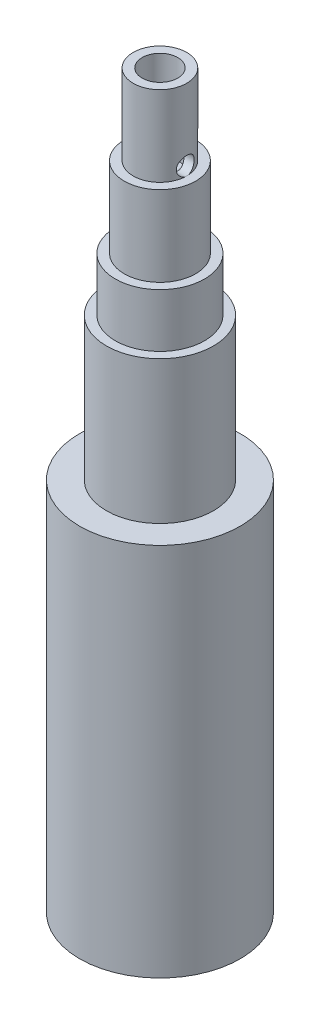
SolidWorks part; units mm, degrees
material "Plain Carbon Steel"
ref_plane "Front Plane" through (0, 0, 0) normal (0, 0, 1) x (1, 0, 0)
ref_plane "Top Plane" through (0, 0, 0) normal (0, 1, 0) x (1, 0, 0)
ref_plane "Right Plane" through (0, 0, 0) normal (1, 0, 0) x (0, 0, -1)
sketch "Sketch1" plane through (0, 0, 0) normal (0, 1, 0) x (1, 0, 0)
  circle A0 centre (0, 0) radius 9
  dimension "D1" = 18
extrude "base section" add sketch "Sketch1" along normal blind 42
sketch "Sketch2" plane through (0, 42, 0) normal (0, 1, 0) x (1, 0, 0)
  circle A0 centre (0, 0) radius 6
  dimension "D1" = 12
extrude "second section" add sketch "Sketch2" along normal blind 16
sketch "Sketch3" plane through (0, 58, 0) normal (0, 1, 0) x (1, 0, 0)
  circle A0 centre (0, 0) radius 5
  dimension "D1" = 10
extrude "bearing section" add sketch "Sketch3" along normal blind 6
sketch "Sketch4" plane through (0, 64, 0) normal (0, 1, 0) x (1, 0, 0)
  circle A0 centre (0, 0) radius 4
  dimension "D1" = 8
extrude "seal section" add sketch "Sketch4" along normal blind 9
sketch "Sketch5" plane through (0, 73, 0) normal (0, 1, 0) x (1, 0, 0)
  circle A0 centre (0, 0) radius 3
  dimension "D1" = 6
extrude "impeller section" add sketch "Sketch5" along normal blind 9
sketch "Sketch6" plane through (0, 82, 0) normal (0, 1, 0) x (1, 0, 0)
  circle A0 centre (0, 0) radius 2
  dimension "D1" = 4
extrude "impeller screw hole" cut sketch "Sketch6" against normal blind 10
sketch "Sketch7" plane through (0, 0, 0) normal (0, -1, 0) x (-1, 0, 0)
  circle A0 centre (0, 0) radius 4
  dimension "D1" = 8
extrude "motor shaft hole" cut sketch "Sketch7" against normal blind 32
sketch "Sketch8" plane through (0, 0, 0) normal (1, 0, 0) x (0, 0, -1)
  line L0 (0, 82) -> (0, 73) construction
  line L1 (3, 82) -> (-3, 82) construction
  line L2 (4, 73) -> (-4, 73) construction
  circle A0 centre (0, 74) radius 1
  dimension "D1" = 2
extrude "impeller dowel hole" cut sketch "Sketch8" against normal blind 10 and the other way blind 10
sketch "Sketch9" plane through (0, 0, 0) normal (1, 0, 0) x (0, 0, -1)
  line L0 (0, 32) -> (0, 0) construction
  line L1 (-4, 32) -> (4, 32) construction
  circle A0 centre (0, 29) radius 3
  circle A1 centre (0, 18.3333) radius 3
  dimension "D1" = 6
  dimension "D2" = 10.6667
extrude "set screw holes" cut sketch "Sketch9" against normal blind 20
equation "\"D1@Sketch1\"=\"coupler shaft base diameter\""
equation "\"bearing OD\" = 20mm"
equation "\"bearing outer race thickness\"= 1mm"
equation "\"bearing ID\"= 10mm"
equation "\"bearing depth\"= 6mm"
equation "\"bearing inner race thickness\"= 1mm"
equation "\"seal OD\" = 20mm"
equation "\"seal ID\"= 8mm"
equation "\"seal depth\"= 6mm"
equation "\"impeller base outer diameter\"= 1.75in"
equation "\"impeller base outer thickness\"= 1mm"
equation "\"impeller base center thickness\"= 5mm"
equation "\"impeller number of vanes\"= 8"
equation "\"impeller vane inner height\"= 8mm"
equation "\"impeller primary vane opening diamater\"= 10mm"
equation "\"impeller vane inner thickness\"= .75mm"
equation "\"impeller vane outer thickness\"= 1.5mm"
equation "\"impeller primary vane entrance angle\"= 20deg"
equation "\"impeller secondary vane entrance angle\"= 20deg"
equation "\"impeller secondary vane opening diameter\"= 10mm"
equation "\"motor to housing distance\"= 60mm"
equation "\"motor mount pattern diameter\"= 30mm"
equation "\"motor mount coupler shaft hole diameter\"= \"coupler shaft base diameter\"+ 4mm"
equation "\"motor mount to housing m8 screw hole diameter\"= 8.5mm"
equation "\"motor mount to housing m8 screw post radius\"= ( 3 * \"motor mount to housing m8 screw hole diameter\" ) / 2"
equation "\"motor mount to housing m8 pattern diameter\"= 100mm"
equation "\"motor mount to housing m4 screw hole diamater\"= 4mm"
equation "\"motor mount to housing m4 head diameter\"= 7.25mm"
equation "\"motor mount to housing m4 head depth\"= 4mm"
equation "\"motor mount plate thickness\"= 6mm + \"motor mount to housing m4 head depth\""
equation "\"motor shaft pride\"= 32mm"
equation "\"motor shaft flat section length from tip\"= 25.7mm"
equation "\"motor shaft bore end clearance\"= 2mm"
equation "\"motor mount shaft hole depth\"= \"motor shaft pride\""
equation "\"coupler shaft set screw drill hole diameter\"= 6mm"
equation "\"coupler shaft motor shaft hole diameter\"= 8mm"
equation "\"coupler shaft base diameter\"= 18mm"
equation "\"coupler shaft base length\"= \"motor mount shaft hole depth\" + 10mm"
equation "\"coupler shaft second section diameter\"= \"bearing ID\" + \"bearing inner race thickness\" * 2"
equation "\"coupler shaft third section diamater\"= \"bearing ID\""
equation "\"coupler shaft second section length\"= \"motor to housing distance\" -  \"coupler shaft base length\" - 2mm"
equation "\"coupler shaft set screw 1 distance\"= \"motor mount shaft hole depth\" / 3"
equation "\"coupler shaft set screw 2 distance\"= \"motor mount shaft hole depth\" * 4 / 5"
equation "\"housing bearing seat lip thickness\" = 2mm"
equation "\"housing base thickness\"= \"housing bearing seat lip thickness\" + \"seal depth\" + \"bearing depth\""
equation "\"housing top impeller vertical clearance\"= .5mm"
equation "\"housing top impeller horizontal clearance\"= .5mm"
equation "\"housing top impeller bottom clearance\"= 1mm"
equation "\"housing top impeller cavity height\"= \"housing top impeller bottom clearance\" + \"impeller base center thickness\" + \"impeller vane inner height\" + \"housing top impeller vertical clearance\""
equation "\"housing top impeller cavity diameter\"= 2 * \"housing top impeller horizontal clearance\" + \"impeller base outer diameter\""
equation "\"housing top impeller cavity tip height\"= \"housing top impeller bottom clearance\" + \"housing top impeller vertical clearance\" + \"impeller base outer thickness\" + \"impeller vane outer height\""
equation "\"housing top entrance OD\"= 20mm"
equation "\"housing top exit OD\"= 5mm"
equation "\"housing top o-ring channel height\"= 1.5mm"
equation "\"housing top o ring channel width\"= 1.5mm"
equation "\"housing top threaded inlet depth\"= 8mm"
equation "\"housing top total thickness\"= \"housing top threaded inlet depth\" + \"housing top impeller cavity height\""
equation "\"housing top total width\"= 10mm"
equation "\"housing top exit threaded diameter\"= 8mm"
equation "\"housing top exit threaded depth\"= 8mm"
equation "\"coupler shaft third section length\"= \"bearing depth\""
equation "\"coupler shaft seal section diameter\" = \"seal ID\""
equation "\"coupler shaft seal section length\" = \"housing base thickness\"+\"housing top impeller bottom clearance\"-\"bearing depth\""
equation "\"coupler shaft impeller section diameter\" = 6mm"
equation "\"coupler shaft impeller section length\" = \"impeller boss depth\"+\"impeller base center thickness\" - 1mm"
equation "\"D1@base section\" = \"coupler shaft base length\""
equation "\"D1@Sketch2\"=\"coupler shaft second section diameter\""
equation "\"D1@second section\" = \"coupler shaft second section length\""
equation "\"D1@Sketch3\"=\"coupler shaft third section diamater\""
equation "\"D1@bearing section\" = \"coupler shaft third section length\""
equation "\"D1@Sketch4\"=\"coupler shaft seal section diameter\""
equation "\"D1@seal section\" = \"coupler shaft seal section length\""
equation "\"D1@Sketch5\"=\"coupler shaft impeller section diameter\""
equation "\"D1@impeller section\" = \"coupler shaft impeller section length\""
equation "\"coupler shaft impeller screw hole diameter\" = \"motor mount to housing m4 screw hole diamater\""
equation "\"coupler shaft impeller screw hole depth\" = 10mm"
equation "\"D1@Sketch6\"=\"coupler shaft impeller screw hole diameter\""
equation "\"D1@impeller screw hole\" = \"coupler shaft impeller screw hole depth\""
equation "\"D1@Sketch7\"=\"coupler shaft motor shaft hole diameter\""
equation "\"D1@motor shaft hole\" = \"motor mount shaft hole depth\""
equation "\"impeller vane outer height\"= 4mm"
equation "\"impeller bolt surface height\" = 5mm"
equation "\"impeller bolt surface diameter\" = 8mm"
equation "\"housing top o-ring circumference\" = 250mm"
equation "\"housing top o-ring radius\" = (\"housing top o-ring circumference\")/(2*3.14)"
equation "\"coupler shaft to motor clearance\" = 2mm"
equation "\"impeller dowel diameter\" = 2mm"
equation "\"impeller dowel length\" = 2mm*2 + \"coupler shaft impeller section diameter\""
equation "\"D1@Sketch8\"=\"impeller dowel diameter\""
equation "\"D1@Sketch9\"=\"coupler shaft set screw drill hole diameter\""
equation "\"D2@Sketch9\"=\"coupler shaft set screw 1 distance\""
equation "\"impeller boss depth\" = 5mm"
equation "\"impeller boss diameter\" = \"coupler shaft impeller section diameter\"+2*5mm"
